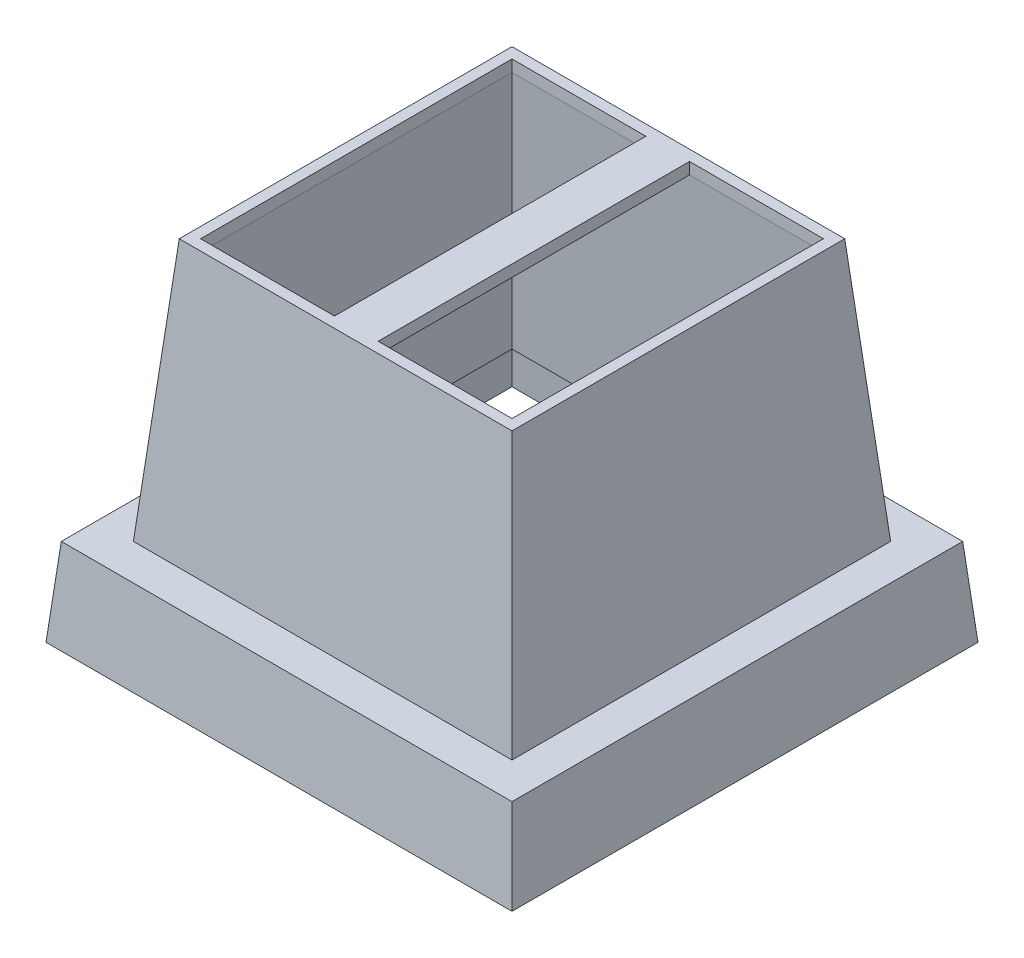
SolidWorks part; units mm, degrees
ref_plane "Front Plane" through (0, 0, 0) normal (0, 0, 1) x (1, 0, 0)
ref_plane "Top Plane" through (0, 0, 0) normal (0, 1, 0) x (1, 0, 0)
ref_plane "Right Plane" through (0, 0, 0) normal (1, 0, 0) x (0, 0, -1)
sketch "Sketch1" plane through (0, 0, 0) normal (0, 1, 0) x (1, 0, 0)
  line L13 (0, 0) -> (-32, 0)
  line L14 (0, 0) -> (0, 32)
  line L15 (0, 32) -> (-32, 32)
  line L16 (-32, 0) -> (-32, 32)
  dimension "D1" = 32
  dimension "D2" = 32
extrude "Boss-Extrude1" add sketch "Sketch1" along normal blind 6 draft 5
sketch "Sketch2" plane through (0, 6, 0) normal (0, 1, 0) x (1, 0, 0)
  line L0 (-31.4751, 0.5249) -> (-0.5249, 0.5249) construction
  line L1 (-29, 29) -> (-3, 29)
  line L2 (-29, 29) -> (-29, 3)
  line L3 (-29, 3) -> (-3, 3)
  line L4 (-3, 29) -> (-3, 3)
  line L5 (-0.5249, 0.5249) -> (-0.5249, 31.4751) construction
  point P4 (-29.5843, 29.5228)
  point P5 (-16, 3)
  point P8 (-16, 0.5249)
  point P9 (-3, 16)
  point P12 (-0.5249, 16)
  dimension "D1" = 26
  dimension "D2" = 26
extrude "Boss-Extrude2" add sketch "Sketch2" along normal blind 18 draft 5
shell "Shell1" thickness 0.8 removed face at (-16, 0, -16)
chamfer "Chamfer1" distance 2.5 angle 45 4 edges at (-16, 5.2, -1.258) (-30.742, 5.2, -16) (-16, 5.2, -30.742) (-1.258, 5.2, -16) first distance on face at (-16, 5.2, -16)
sketch "Sketch3" plane through (0, 23.2, 0) normal (0, -1, 0) x (1, 0, 0)
  line L0 (-5.3079, -26.6921) -> (-26.6921, -26.6921) construction
  line L1 (-17.5, -5.3079) -> (-14.5, -5.3079)
  line L2 (-17.5, -5.3079) -> (-17.5, -26.6921)
  line L3 (-17.5, -26.6921) -> (-14.5, -26.6921)
  line L4 (-14.5, -5.3079) -> (-14.5, -26.6921)
  line L5 (-26.6921, -5.3079) -> (-5.3079, -5.3079) construction
  line L7 (-17.5, -5.3079) -> (-26.6921, -5.3079)
  line L8 (-17.5, -5.3079) -> (-17.5, -26.6921)
  line L9 (-17.5, -26.6921) -> (-26.6921, -26.6921)
  line L10 (-26.6921, -5.3079) -> (-26.6921, -26.6921)
  line L11 (-14.5, -5.3079) -> (-5.3079, -5.3079)
  line L12 (-14.5, -5.3079) -> (-14.5, -26.6921)
  line L13 (-14.5, -26.6921) -> (-5.3079, -26.6921)
  line L14 (-5.3079, -5.3079) -> (-5.3079, -26.6921)
  point P6 (-16, -5.3079)
  point P9 (-16, -5.3079)
  point P15 (-13.5649, -5.3079)
  line M13 (-26.6921, -5.3079) -> (-26.6921, -26.6921)
  line M14 (-26.6921, -26.6921) -> (-5.3079, -26.6921)
  line M15 (-5.3079, -26.6921) -> (-5.3079, -5.3079)
  line M16 (-5.3079, -5.3079) -> (-26.6921, -5.3079)
  dimension "D1" = 3
extrude "Cut-Extrude1" cut sketch "Sketch3" against normal through all contours L2 M16 M13 M14 | L4 M16 M14 M15 region at (-22.0961, 23.2, -16) region at (-9.9039, 23.2, -16)
equation "\"D2@Sketch1\"=\"D1@Sketch1\""
equation "\"D2@Sketch2\"=\"D1@Sketch2\""
